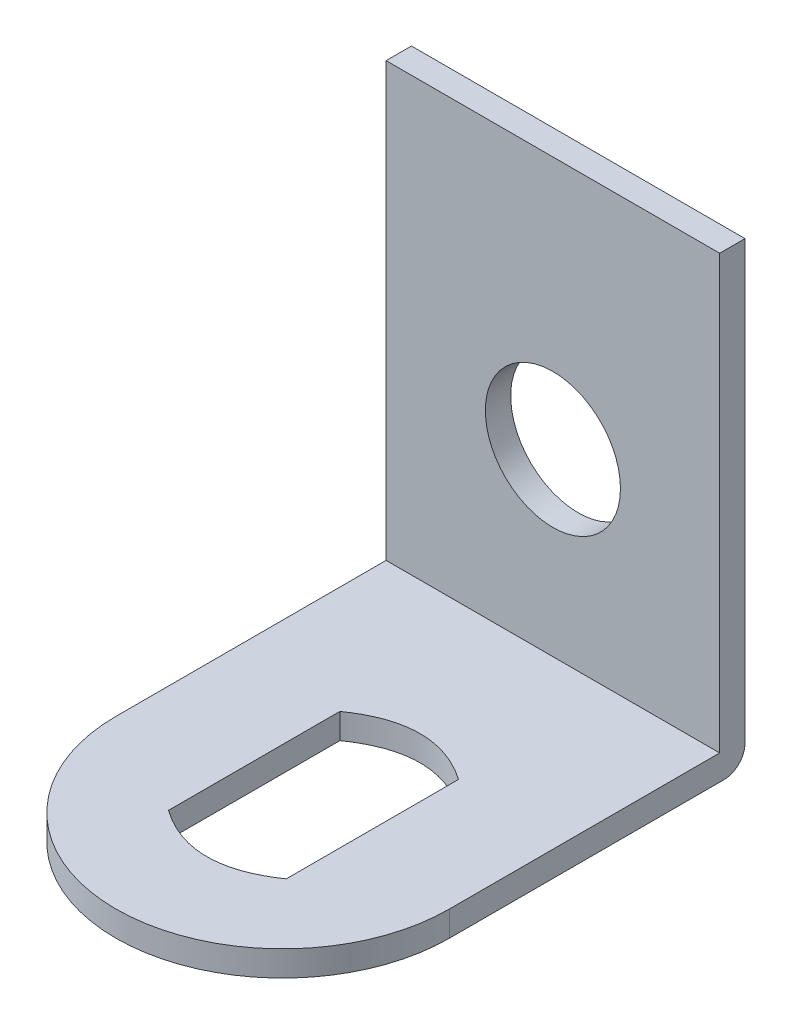
SolidWorks part; units mm, degrees
ref_plane "Front Plane" through (0, 0, 0) normal (0, 0, 1) x (1, 0, 0)
ref_plane "Top Plane" through (0, 0, 0) normal (0, 1, 0) x (1, 0, 0)
ref_plane "Right Plane" through (0, 0, 0) normal (1, 0, 0) x (0, 0, -1)
sketch "Sketch3" plane through (0, 0, 0) normal (1, 0, 0) x (0, 0, -1)
  line L0 (0, 0) -> (-21.9, 0)
  line L2 (0, 0) -> (0, 21.7)
  line L4 (-1.2, 1.2) -> (-1.2, 21.7)
  line L5 (-1.2, 21.7) -> (0, 21.7)
  line L6 (-21.9, 0) -> (-21.9, 1.2)
  line L7 (-21.9, 1.2) -> (-1.2, 1.2)
  dimension "D2" = 1.2
extrude "Boss-Extrude1" add sketch "Sketch3" along normal blind 7.9 and the other way blind 7.9
fillet "Fillet1" 2 edges at (7.9, 0.6, 21.9) (-7.9, 0.6, 21.9) type full round first side face at (7.9, 7.6333, 7.7) second side face at (-7.9, 7.6333, 7.7) middle face at (0, 0.6, 21.9)
sketch "Sketch4" plane through (0, 1.2, 0) normal (0, 1, 0) x (1, 0, 0)
  line L4 (-2.8, -8.4903) -> (-2.8, -16.6097)
  line L6 (2.8, -8.4701) -> (2.8, -16.6299)
  spline S0 degree 2 poles (2.8, -8.4701) (-0.0063, -6.5198) (-2.8, -8.4903) knots 0 0 0 1 1 1
  spline S1 degree 2 poles (2.8, -16.6299) (-0.0063, -18.5802) (-2.8, -16.6097) knots 0 0 0 1 1 1
  point P7 (0, -12.55)
extrude "Cut-Extrude3" cut sketch "Sketch4" against normal through all
sketch "Sketch5" plane through (0, 0, 1.2) normal (0, 0, 1) x (1, 0, 0)
  line L0 (-7.9, 21.7) -> (7.9, 21.7) construction
  circle A0 centre (0, 9.7) radius 3.2
extrude "Cut-Extrude4" cut sketch "Sketch5" against normal through all
fillet "Fillet3" radius 1 1 edges at (0, 0, 0) type face fillet first side face at (0, 0, 12.545) second side face at (3.2, 9.7, 0)
